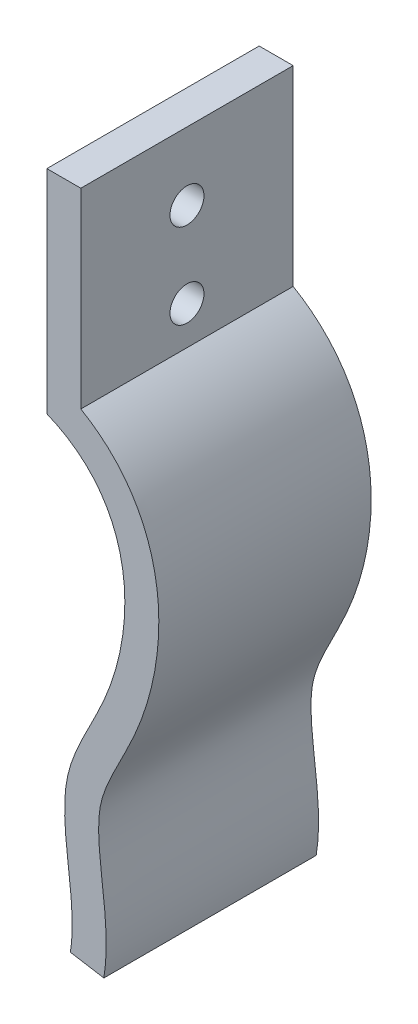
SolidWorks part; units mm, degrees
ref_plane "Ön Düzlem" through (0, 0, 0) normal (0, 0, 1) x (1, 0, 0)
ref_plane "Üst Düzlem" through (0, 0, 0) normal (0, 1, 0) x (1, 0, 0)
ref_plane "Sağ Düzlem" through (0, 0, 0) normal (1, 0, 0) x (0, 0, -1)
sketch "Çizim1" plane through (0, 0, 0) normal (0, 0, 1) x (1, 0, 0)
  line L0 (0, 46.8099) -> (0, 21.8099)
  line L1 (4, 46.8099) -> (4, 24.2964)
  line L2 (0, 46.8099) -> (4, 46.8099)
  line L3 (2.7684, -31.7069) -> (6.7145, -32.3612)
  spline S0 degree 3 poles (0, 21.8099) (10.5687, 17.4853) (10.8615, 0.8206) (0.9983, -13.7254) (2.7959, -23.6402) (3.1211, -29.5799) (2.7684, -31.7069) knots 0 0 0 0 0.502232 0.695448 0.885833 1 1 1 1
  spline S1 degree 1 poles (4, 24.2964) (6.7145, -32.3612) knots 0 0 1 1 construction
  spline S2 degree 3 poles (4, 24.2964) (4.6852, 23.9004) (6.022, 23.0113) (8.3339, 20.9926) (10.609, 18.0309) (12.3264, 14.0662) (13.1595, 9.9108) (13.2499, 5.7018) (12.7186, 1.5308) (11.8331, -1.8486) (10.899, -4.4521) (9.8104, -6.9845) (8.3727, -9.7588) (7.2043, -12.1465) (6.5751, -13.8552) (6.2779, -15.001) (6.1214, -16.211) (6.0652, -18.048) (6.2666, -20.675) (6.7224, -24.2353) (7.0119, -27.48) (6.9828, -30.2151) (6.8312, -31.6574) (6.7145, -32.3612) knots 0.033865 0.033865 0.033865 0.033865 0.064056 0.094248 0.154631 0.215015 0.275398 0.335782 0.396165 0.456549 0.486741 0.516932 0.577316 0.637699 0.667891 0.698083 0.728274 0.758466 0.81885 0.879233 0.939617 0.969808 1 1 1 1
  dimension "D2" = 25
  dimension "D1" = 4
extrude "Yükseklik-Ekstrüzyon1" add sketch "Çizim1" along normal blind 25
sketch "Çizim2" plane through (4, 0, 0) normal (1, 0, 0) x (0, 0, -1)
  line L0 (-25, 24.2964) -> (-25, 46.8099) construction
  line L1 (-25, 46.8099) -> (0, 46.8099) construction
  circle A0 centre (-12.5, 38.8099) radius 2
  circle A1 centre (-12.5, 28.8099) radius 2
  dimension "D1" = 12.5
  dimension "D3" = 10
  dimension "D2" = 8
extrude "Kes-Ekstrüzyon1" cut sketch "Çizim2" against normal blind 25
